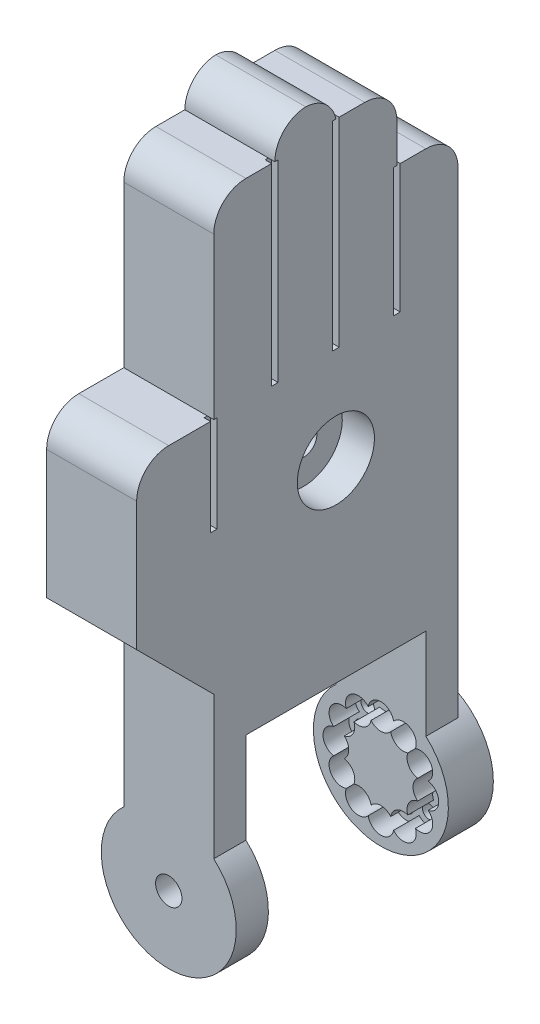
SolidWorks part; units mm, degrees
material "Esun Hard Tough Resin"
ref_plane "Front Plane" through (0, 0, 0) normal (0, 0, 1) x (1, 0, 0)
ref_plane "Top Plane" through (0, 0, 0) normal (0, 1, 0) x (1, 0, 0)
ref_plane "Right Plane" through (0, 0, 0) normal (1, 0, 0) x (0, 0, -1)
sketch "Sketch2" plane through (0, 0, 0) normal (0, 0, 1) x (1, 0, 0)
  circle A0 centre (0, 0) radius 10.5
  dimension "D1" = 21
extrude "Boss-Extrude1" add sketch "Sketch2" along normal blind 40
sketch "Sketch4" plane through (0, 0, 40) normal (0, 0, 1) x (1, 0, 0)
  line L1 (-7, 0) -> (7, 0)
  line L2 (-7, 0) -> (-7, 22)
  line L3 (-7, 22) -> (7, 22)
  line L4 (7, 0) -> (7, 22)
  point P4 (0, 0)
  dimension "D1" = 14
  dimension "D2" = 22
extrude "Boss-Extrude2" add sketch "Sketch4" against normal blind 38
sketch "Sketch5" plane through (7, 0, 0) normal (1, 0, 0) x (0, 0, -1)
  line L0 (-2, 22) -> (-40, 22) construction
  line L1 (-35, 22) -> (-7, 22)
  line L2 (-35, 22) -> (-35, -10.5)
  line L3 (-35, -10.5) -> (-7, -10.5)
  line L4 (-7, 22) -> (-7, -10.5)
  line L5 (-40, -10.5) -> (0, -10.5) construction
  line L6 (-40, 7.8262) -> (-40, 22) construction
  line L7 (-2, 7.8262) -> (-2, 22) construction
  dimension "D1" = 5
  dimension "D2" = 5
extrude "Cut-Extrude1" cut sketch "Sketch5" against normal through all both and the other way through all
sketch "Sketch6" plane through (0, 22, 0) normal (0, 1, 0) x (1, 0, 0)
  line L1 (-7, -2) -> (7, -2)
  line L2 (-7, -2) -> (-7, -40)
  line L3 (-7, -40) -> (7, -40)
  line L4 (7, -2) -> (7, -40)
extrude "Boss-Extrude3" add sketch "Sketch6" along normal blind 40
sketch "Sketch7" plane through (7, 0, 0) normal (1, 0, 0) x (0, 0, -1)
  line L0 (-40, 62) -> (-40, 7.8262) construction
  line L1 (-40, 42) -> (-52, 42)
  line L2 (-40, 42) -> (-40, 67)
  line L3 (-40, 67) -> (-52, 67)
  line L4 (-52, 42) -> (-52, 67)
  line L5 (-40, 62) -> (-2, 62) construction
  line L6 (-40, 62) -> (-30.5, 62)
  line L7 (-40, 62) -> (-40, 97)
  line L8 (-40, 97) -> (-30.5, 97)
  line L9 (-30.5, 62) -> (-30.5, 97)
  line L10 (-30.5, 62) -> (-21, 62)
  line L11 (-30.5, 62) -> (-30.5, 102)
  line L12 (-30.5, 102) -> (-21, 102)
  line L13 (-21, 62) -> (-21, 102)
  line L14 (-52, 42) -> (-40, 30)
  line L15 (-21, 62) -> (-11.5, 62)
  line L16 (-21, 62) -> (-21, 98)
  line L17 (-21, 98) -> (-11.5, 98)
  line L18 (-11.5, 62) -> (-11.5, 98)
  line L19 (-11.5, 62) -> (-2, 62)
  line L20 (-11.5, 62) -> (-11.5, 87)
  line L21 (-11.5, 87) -> (-2, 87)
  line L22 (-2, 62) -> (-2, 87)
  line L23 (-40, 30) -> (-40, 42)
  line L24 (-52, 42) -> (-40, 42)
  dimension "D1" = 40
  dimension "D2" = 35
  dimension "D3" = 36
  dimension "D4" = 25
  dimension "D5" = 12
  dimension "D6" = 25
  dimension "D7" = 5
extrude "Boss-Extrude4" add sketch "Sketch7" along direction (-1, 0, 0) on the side against the normal blind 14 contours L2 L1 L4 L3 | L7 L6 L9 L8 | L11 L10 L13 L12 | L16 L15 L18 L17 | L20 L19 L22 L21
sketch "Sketch8" plane through (7, 0, 0) normal (1, 0, 0) x (0, 0, -1)
  line L0 (-52, 42) -> (-40, 30)
  line L1 (-40, 42) -> (-40, 7.8262) construction
  line L2 (-40, 30) -> (-40, 42)
  line L3 (-40, 42) -> (-52, 42)
extrude "Boss-Extrude5" add sketch "Sketch8" against normal blind 14
sketch "Sketch9" plane through (7, 0, 0) normal (1, 0, 0) x (0, 0, -1)
  line L6 (-31, 97) -> (-30, 97)
  line L7 (-31, 97) -> (-31, 67)
  line L8 (-31, 67) -> (-30, 67)
  line L9 (-30, 97) -> (-30, 67)
  line L10 (-21.5, 98) -> (-20.5, 98)
  line L11 (-21.5, 98) -> (-21.5, 67)
  line L12 (-21.5, 67) -> (-20.5, 67)
  line L13 (-20.5, 98) -> (-20.5, 67)
  line L14 (-12, 87) -> (-11, 87)
  line L15 (-12, 87) -> (-12, 67)
  line L16 (-12, 67) -> (-11, 67)
  line L17 (-11, 87) -> (-11, 67)
  line L18 (-40, 67) -> (-52, 67) construction
  line L19 (-40.5, 67) -> (-39.5, 67)
  line L20 (-40.5, 67) -> (-40.5, 52)
  line L21 (-40.5, 52) -> (-39.5, 52)
  line L22 (-39.5, 67) -> (-39.5, 52)
  point P0 (-30.5, 97)
  point P1 (-21, 98)
  point P2 (-11.5, 87)
  point P22 (-40, 67)
  dimension "D1" = 1
  dimension "D2" = 15
extrude "Cut-Extrude2" cut sketch "Sketch9" against normal blind 1
fillet "Fillet1" radius 5 6 edges at (0, 67, 52) (0, 97, 40) (0, 102, 30.5) (0, 102, 21) (0, 98, 11.5) (0, 87, 2)
sketch "Sketch10" plane through (-7, 0, 0) normal (-1, 0, 0) x (0, 0, 1)
  line L0 (52, 42) -> (52, 62) construction
  circle A0 centre (21, 52) radius 12.5
  point P4 (52, 52)
  dimension "D1" = 25
extrude "Cut-Extrude3" cut sketch "Sketch10" against normal blind 6
sketch "Sketch11" plane through (-1, 0, 0) normal (-1, 0, 0) x (0, 0, 1)
  circle A0 centre (21, 52) radius 2.05
  dimension "D1" = 4.1
extrude "Cut-Extrude4" cut sketch "Sketch11" against normal through all
sketch "Sketch12" plane through (7, 0, 0) normal (1, 0, 0) x (0, 0, -1)
  circle A0 centre (-21, 52) radius 6
  dimension "D1" = 12
extrude "Cut-Extrude5" cut sketch "Sketch12" against normal blind 5
sketch "Sketch13" plane through (0, 0, 40) normal (0, 0, 1) x (1, 0, 0)
  circle A0 centre (0, 0) radius 2.05
  dimension "D1" = 4.1
extrude "Cut-Extrude6" cut sketch "Sketch13" against normal up to next
sketch "Sketch14" plane through (0, 0, 35) normal (0, 0, -1) x (-1, 0, 0)
  circle A0 centre (0, 0) radius 4.5
  dimension "D1" = 9
extrude "Cut-Extrude7" cut sketch "Sketch14" against normal blind 2
sketch "Sketch15" plane through (0, 0, 7) normal (0, 0, 1) x (1, 0, 0)
  line L0 (0, 7) -> (0, -7) construction
  line L1 (-7, 0) -> (7, 0) construction
  line L2 (-3.5, 6.0622) -> (3.5, -6.0622) construction
  line L3 (-6.0622, 3.5) -> (6.0622, -3.5) construction
  line L4 (-6.0622, -3.5) -> (6.0622, 3.5) construction
  line L5 (-3.5, -6.0622) -> (3.5, 6.0622) construction
  circle A0 centre (0, 0) radius 7 construction
  circle A1 centre (-6.0622, 3.5) radius 1.05
  circle A2 centre (-6.0622, -3.5) radius 1.05
  circle A3 centre (-3.5, -6.0622) radius 1.05
  circle A4 centre (0, -7) radius 1.05
  circle A5 centre (3.5, -6.0622) radius 1.05
  circle A6 centre (6.0622, -3.5) radius 1.05
  circle A7 centre (7, 0) radius 1.05
  circle A8 centre (6.0622, 3.5) radius 1.05
  circle A9 centre (3.5, 6.0622) radius 1.05
  circle A10 centre (0, 7) radius 1.05
  circle A11 centre (-3.5, 6.0622) radius 1.05
  circle A12 centre (-7, 0) radius 1.05
  dimension "D1" = 14
  dimension "D6" = 2.1
  dimension "D2" = 30
  dimension "D3" = 30
  dimension "D4" = 30
  dimension "D5" = 30
extrude "Cut-Extrude8" cut sketch "Sketch15" against normal through all
sketch "Sketch17" plane through (0, 0, 7) normal (0, 0, 1) x (1, 0, 0)
  circle A0 centre (0, 7) radius 2
  circle A1 centre (3.5, 6.0622) radius 2
  circle A2 centre (-3.5, 6.0622) radius 2
  circle A3 centre (-6.0622, 3.5) radius 2
  circle A4 centre (-7, 0) radius 2
  circle A5 centre (-6.0622, -3.5) radius 2
  circle A6 centre (-3.5, -6.0622) radius 2
  circle A7 centre (0, -7) radius 2
  circle A8 centre (3.5, -6.0622) radius 2
  circle A9 centre (6.0622, -3.5) radius 2
  circle A10 centre (7, 0) radius 2
  circle A11 centre (6.0622, 3.5) radius 2
  dimension "D1" = 4
extrude "Cut-Extrude9" cut sketch "Sketch17" against normal blind 4 contours A3 | A2 | A4 | A5 | A0 | A1 | A11 | A10 | A9 | A8 | A7 | A6
